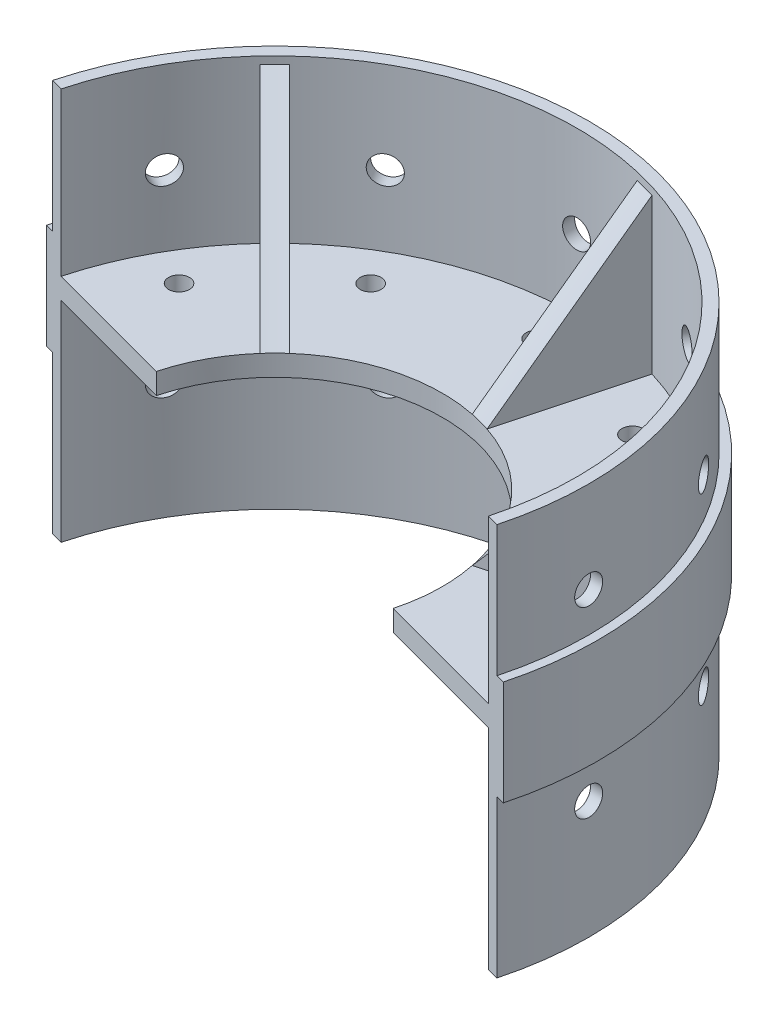
SolidWorks part; units mm, degrees
material "2024-T4"
ref_plane "Front Plane" through (0, 0, 0) normal (0, 0, 1) x (1, 0, 0)
ref_plane "Top Plane" through (0, 0, 0) normal (0, 1, 0) x (1, 0, 0)
ref_plane "Right Plane" through (0, 0, 0) normal (1, 0, 0) x (0, 0, -1)
sketch "Sketch1" plane through (0, 0, 0) normal (0, 1, 0) x (1, 0, 0)
  circle A0 centre (0, 0) radius 73.279
  circle A1 centre (0, 0) radius 78.359
  dimension "D1" = 146.558
  dimension "D2" = 156.718
extrude "Boss-Extrude1" add sketch "Sketch1" along normal blind 25.4
sketch "Sketch2" plane through (0, 25.4, 0) normal (0, 1, 0) x (1, 0, 0)
  circle A0 centre (0, 0) radius 76.2
  circle A1 centre (0, 0) radius 73.279
  circle A2 centre (0, 0) radius 73.279 construction
  dimension "D1" = 0
extrude "Boss-Extrude2" add sketch "Sketch2" along normal blind 31.75
sketch "Sketch3" plane through (0, 0, 0) normal (0, -1, 0) x (1, 0, 0)
  circle A0 centre (0, 0) radius 76.2
  circle A1 centre (0, 0) radius 73.279
  circle A2 centre (0, 0) radius 73.279 construction
  dimension "D1" = 152.4
  dimension "D2" = 0
extrude "Boss-Extrude3" add sketch "Sketch3" along normal blind 38.1
ref_plane "Plane1" through (0, 12.7, 0) normal (0, 1, 0) x (1, 0, 0)
sketch "Sketch4" plane through (0, 12.7, 0) normal (0, 1, 0) x (1, 0, 0)
  circle A0 centre (0, 0) radius 74.549
  circle A1 centre (0, 0) radius 40.64
  dimension "D1" = 81.28
extrude "Boss-Extrude4" add sketch "Sketch4" along normal blind 5.08
sketch "Sketch5" plane through (0, 17.78, 0) normal (0, 1, 0) x (1, 0, 0)
  line L3 (0, 0) -> (40.64, 0) construction
  line L35 (38.5211, 12.9513) -> (70.0821, 21.4081)
  line L36 (39.8359, 8.0444) -> (71.3969, 16.5012)
  line L37 (70.7821, 18.966) -> (0, 0) construction
  line L38 (26.8846, -30.4767) -> (49.9889, -53.581)
  line L39 (30.4767, -26.8846) -> (53.581, -49.9889)
  line L40 (-12.9513, -38.5211) -> (-21.4081, -70.0821)
  line L41 (-8.0444, -39.8359) -> (-16.5012, -71.3969)
  line L42 (-39.8359, -8.0444) -> (-71.3969, -16.5012)
  line L43 (-38.5211, -12.9513) -> (-70.0821, -21.4081)
  line L44 (-26.8846, 30.4767) -> (-49.9889, 53.581)
  line L45 (-30.4767, 26.8846) -> (-53.581, 49.9889)
  line L46 (12.9513, 38.5211) -> (21.4081, 70.0821)
  line L47 (8.0444, 39.8359) -> (16.5012, 71.3969)
  circle A0 centre (0, 0) radius 40.64 construction
  circle A3 centre (0, 0) radius 73.279 construction
  arc A34 (70.0821, 21.4081) -> (71.3969, 16.5012) centre (0, 0) cw
  arc A35 (38.5211, 12.9513) -> (39.8359, 8.0444) centre (0, 0) cw
  arc A36 (30.4767, -26.8846) -> (26.8846, -30.4767) centre (0, 0) cw
  arc A37 (53.581, -49.9889) -> (49.9889, -53.581) centre (0, 0) cw
  arc A38 (-8.0444, -39.8359) -> (-12.9513, -38.5211) centre (0, 0) cw
  arc A39 (-16.5012, -71.3969) -> (-21.4081, -70.0821) centre (0, 0) cw
  arc A40 (-38.5211, -12.9513) -> (-39.8359, -8.0444) centre (0, 0) cw
  arc A41 (-70.0821, -21.4081) -> (-71.3969, -16.5012) centre (0, 0) cw
  arc A42 (-30.4767, 26.8846) -> (-26.8846, 30.4767) centre (0, 0) cw
  arc A43 (-53.581, 49.9889) -> (-49.9889, 53.581) centre (0, 0) cw
  arc A44 (8.0444, 39.8359) -> (12.9513, 38.5211) centre (0, 0) cw
  arc A45 (16.5012, 71.3969) -> (21.4081, 70.0821) centre (0, 0) cw
  point P29 (0, 0)
  point P34 (0, 0)
  point P40 (0, 0)
  point P42 (39.2552, 10.5184)
  dimension "D1" = 15
  dimension "D2" = 6
  dimension "D5" = 5.08
extrude "Boss-Extrude10" add sketch "Sketch5" along normal blind 38.862
chamfer "Chamfer1" distance 38.862 distance2 33.782 6 edges at (-39.2552, 56.642, 10.5184) (-10.5184, 56.642, 39.2552) (28.7368, 56.642, 28.7368) (39.2552, 56.642, -10.5184) (10.5184, 56.642, -39.2552) (-28.7368, 56.642, -28.7368) first distance on face at (0, 37.211, 0)
sketch "Sketch7" plane through (0, 0, 0) normal (0, 0, 1) x (1, 0, 0)
  line L0 (0, 42.3302) -> (0, 74.728) construction
  line L1 (78.359, 25.4) -> (-78.359, 25.4) construction
  line L2 (-78.359, 12.7) -> (83.2334, 12.7) construction
  line L3 (-78.359, 25.4) -> (-78.359, 0) construction
  circle A0 centre (0, 34.925) radius 3.3909
  circle A1 centre (0, -9.525) radius 3.3909
  dimension "D1" = 6.7818
  dimension "D2" = 9.525
extrude "Cut-Extrude2" cut sketch "Sketch7" against normal through all
ref_axis "Axis1" through (0, 42.3302, 0) along (0, 1, 0)
pattern_circular "CirPattern2" count 12 over 360 about axis through (0, 42.3302, 0) along (0, 1, 0) of "Cut-Extrude2"
sketch "Sketch8" plane through (0, 17.78, 0) normal (0, 1, 0) x (1, 0, 0)
  circle A0 centre (0, 63.5) radius 2.54
  circle A1 centre (31.75, 54.9926) radius 2.54
  circle A2 centre (54.9926, 31.75) radius 2.54
  circle A3 centre (63.5, 0) radius 2.54
  circle A4 centre (54.9926, -31.75) radius 2.54
  circle A5 centre (31.75, -54.9926) radius 2.54
  circle A6 centre (0, -63.5) radius 2.54
  circle A7 centre (-31.75, -54.9926) radius 2.54
  circle A8 centre (-54.9926, -31.75) radius 2.54
  circle A9 centre (-63.5, 0) radius 2.54
  circle A10 centre (-54.9926, 31.75) radius 2.54
  circle A11 centre (-31.75, 54.9926) radius 2.54
  point P27 (0, 0)
  dimension "D1" = 5.08
  dimension "D2" = 63.5
  dimension "D3" = 0
  dimension "D4" = 12
extrude "Cut-Extrude3" cut sketch "Sketch8" against normal up to next
sketch "Sketch9" plane through (0, 17.78, 0) normal (0, 1, 0) x (1, 0, 0)
  line L0 (39.2552, -10.5184) -> (-85.3799, 22.8775) construction
  line L1 (39.2552, -10.5184) -> (110.746, -29.6743) construction
  line L2 (-81.7143, 21.8953) -> (90.8117, -24.3329)
  line L3 (90.8117, -24.3329) -> (54.5481, -86.9792)
  line L4 (54.5481, -86.9792) -> (-98.144, -74.751)
  line L5 (-98.144, -74.751) -> (-81.7143, 21.8953)
  arc A1 (30.4767, -26.8846) -> (39.8359, 8.0444) centre (0, 0) ccw construction
extrude "Cut-Extrude4" cut sketch "Sketch9" against normal through all both and the other way through all
